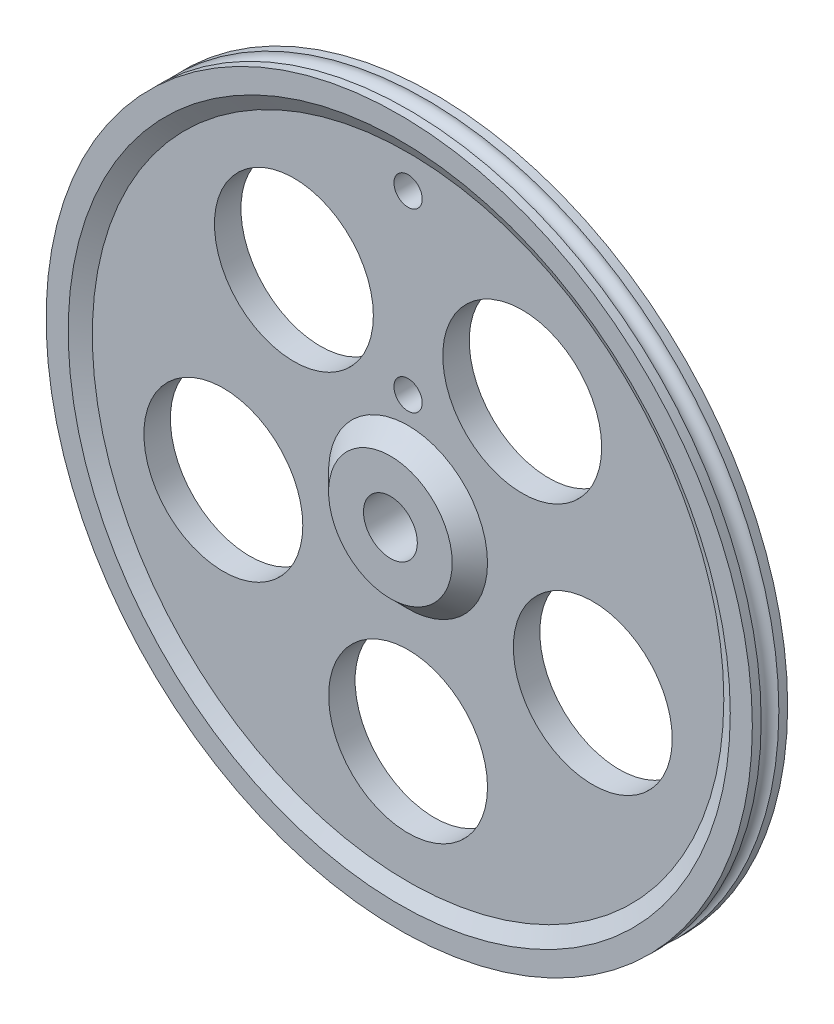
SolidWorks part; units mm, degrees
ref_plane "Front Plane" through (0, 0, 0) normal (0, 0, 1) x (1, 0, 0)
ref_plane "Top Plane" through (0, 0, 0) normal (0, 1, 0) x (1, 0, 0)
ref_plane "Right Plane" through (0, 0, 0) normal (1, 0, 0) x (0, 0, -1)
sketch "Sketch2" plane through (0, 0, 0) normal (0, 1, 0) x (1, 0, 0)
  line L0 (0, 0) -> (64.1086, 0) construction
  line L1 (0, -2) -> (0, -3)
  line L2 (40, -2) -> (0, -2)
  line L3 (40, -2) -> (40, 2)
  line L4 (40, 2) -> (0, 2)
  line L5 (0, -2) -> (0, 2)
  line L6 (40, -2) -> (0, 2) construction
  line L7 (40, 2) -> (0, -2) construction
  line L8 (0, -3) -> (7, -3)
  line L9 (7, -3) -> (7, -1)
  line L10 (7, -1) -> (35.7679, -1)
  line L11 (35.7679, -1) -> (37.5, -2)
  circle A0 centre (40, 0) radius 1
  point P3 (20, 0)
  dimension "D3" = 2
  dimension "D1" = 4
  dimension "D2" = 40
  dimension "D4" = 7
  dimension "D5" = 1
  dimension "D6" = 2.5
  dimension "D7" = 30
  dimension "D8" = 5
revolve "Revolve1" add sketch "Sketch2" angle 360 about L5 region at (3.5, 0, 2.5) region at (19.3422, 0, -0.3462)
sketch "Sketch3" plane through (0, 0, 3) normal (0, 0, 1) x (1, 0, 0)
  circle A0 centre (0, 0) radius 3.05
  dimension "D1" = 6.1
extrude "Cut-Extrude1" cut sketch "Sketch3" against normal through all
chamfer "Chamfer1" distance 2 angle 45 1 edges at (7, 0, 1)
sketch "Sketch4" plane through (0, 0, 1) normal (0, 0, 1) x (1, 0, 0)
  line L0 (0, 0) -> (0, -35.7679) construction
  circle A0 centre (0, 0) radius 35.7679 construction
  circle A1 centre (0, -22) radius 9
  circle A2 centre (-20.9232, -6.7984) radius 9
  circle A3 centre (-12.9313, 17.7984) radius 9
  circle A4 centre (12.9313, 17.7984) radius 9
  circle A5 centre (20.9232, -6.7984) radius 9
  point P18 (0, 0)
  dimension "D1" = 18
  dimension "D2" = 22
  dimension "D3" = 5
extrude "Cut-Extrude2" cut sketch "Sketch4" against normal through all
sketch "Sketch5" plane through (0, 0, -2) normal (0, 0, -1) x (-1, 0, 0)
  line L0 (0, 0) -> (0, 40) construction
  circle A0 centre (0, 0) radius 40 construction
  circle A1 centre (0, 12) radius 1.6
  circle A2 centre (0, 32) radius 1.6
  dimension "D1" = 20
  dimension "D2" = 3.2
  dimension "D3" = 3.2
  dimension "D4" = 12
extrude "Cut-Extrude3" cut sketch "Sketch5" against normal through all
